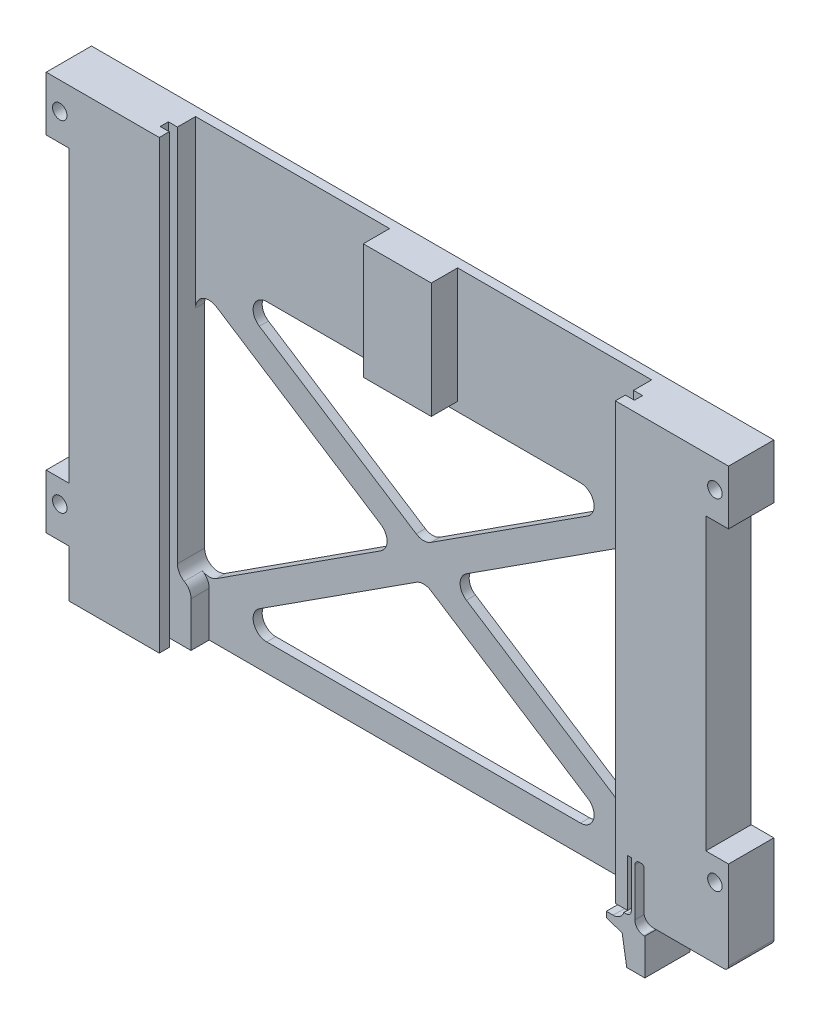
SolidWorks part; units mm, degrees
note: The reader was unsure of these and kept them because the rebuilt part matched: shared geometry of "Sketch4<4>", "Sketch4<3>".
ref_plane "Front Plane" through (0, 0, 0) normal (0, 0, 1) x (1, 0, 0)
ref_plane "Top Plane" through (0, 0, 0) normal (0, 1, 0) x (1, 0, 0)
ref_plane "Right Plane" through (0, 0, 0) normal (1, 0, 0) x (0, 0, -1)
sketch "Sketch2" plane through (0, 0, 0) normal (0, 0, 1) x (1, 0, 0)
  line L4 (140.5, 0) -> (0, 0)
  line L6 (0, 0) -> (0, 98.5)
  line L7 (0, 98.5) -> (140.5, 98.5)
  line L8 (140.5, 98.5) -> (140.5, 0)
  point P2 (0, 0)
  point P5 (20.0537, 0)
  point P6 (0, 0)
  point P7 (154.1532, 0)
  point P8 (0, 0)
  dimension "D1" = 98.5
  dimension "D2" = 140.5
extrude "Boss-Extrude6" add sketch "Sketch2" along normal blind 10
sketch "Sketch1" plane through (0, 0, 0) normal (0, 0, 1) x (1, 0, 0)
  line L1 (20.45, 0) -> (120.05, 0)
  line L2 (17.95, 2.5) -> (17.95, 70.5)
  line L3 (20.45, 73) -> (120.05, 73)
  line L4 (122.55, 2.5) -> (122.55, 70.5)
  line L5 (0, 0) -> (140.5, 0) construction
  line L7 (140.5, 98.5) -> (0, 98.5) construction
  arc A0 (20.45, 0) -> (17.95, 2.5) centre (20.45, 2.5) cw
  arc A1 (17.95, 70.5) -> (20.45, 73) centre (20.45, 70.5) cw
  arc A2 (120.05, 73) -> (122.55, 70.5) centre (120.05, 70.5) cw
  arc A3 (120.05, 0) -> (122.55, 2.5) centre (120.05, 2.5) ccw
  point P7 (17.95, 0)
  point P13 (122.55, 73)
  point P16 (122.55, 0)
  point P21 (70.25, 73)
  point P24 (70.25, 98.5)
  dimension "D3" = 2.5
  dimension "D1" = 104.6
  dimension "D2" = 73
sketch "Sketch10" plane through (0, 0, 0) normal (0, 0, -1) x (-1, 0, 0)
  line L1 (-120.55, 0) -> (-19.95, 0)
  line L2 (-120.55, 0) -> (-120.55, 71)
  line L3 (-120.55, 71) -> (-19.95, 71)
  line L4 (-19.95, 0) -> (-19.95, 71)
  line L6 (0, 0) -> (-140.5, 0) construction
  line L10 (-122.55, 2.5) -> (-122.55, 70.5) construction
  line L11 (-20.45, 73) -> (-120.05, 73) construction
  line L12 (-17.95, 2.5) -> (-17.95, 70.5) construction
  point P4 (-134.9452, 0)
  dimension "D1" = 2
  dimension "D2" = 2
  dimension "D3" = 2
extrude "Cut-Extrude4" cut sketch "Sketch10" against normal through all
sketch "Sketch6" plane through (0, 0, 0) normal (0, 0, 1) x (1, 0, 0)
  line L9 (70.25, 17.5) -> (70.25, 98.5) construction
  line L10 (-2, 92.5) -> (142.5, 92.5) construction
  line L11 (-2, 92.5) -> (-2, 17.5) construction
  line L12 (-2, 17.5) -> (142.5, 17.5) construction
  line L13 (142.5, 92.5) -> (142.5, 17.5) construction
  line L14 (140.5, 98.5) -> (0, 98.5) construction
  circle A4 centre (-2, 92.5) radius 1.6
  circle A5 centre (142.5, 92.5) radius 1.6
  circle A6 centre (142.5, 17.5) radius 1.6
  circle A7 centre (-2, 17.5) radius 1.6
  dimension "D1" = 144.5
  dimension "D4" = 3.2
  dimension "D2" = 75
  dimension "D3" = 17.5
sketch "Sketch3" plane through (0, 0, 0) normal (0, -1, 0) x (1, 0, 0)
  line L0 (70.25, 6) -> (70.25, 0) construction
  line L6 (54.175, 0) -> (-54.175, 0) construction
  line L7 (20.45, 0) -> (120.05, 0) construction
  line L10 (17.95, 7.8) -> (122.55, 7.8)
  line L11 (17.95, 7.8) -> (17.95, 6)
  line L12 (17.95, 6) -> (122.55, 6)
  line L13 (122.55, 7.8) -> (122.55, 6)
  point P5 (70.25, 10)
  point P7 (68.3695, 20.9753)
  point P8 (65.7278, 31.6392)
  point P11 (70.25, 0)
  dimension "D1" = 1.8
  dimension "D2" = 6
extrude "Cut-Extrude1" cut sketch "Sketch3" against normal through all contours L10 L13 L12 L11
sketch "Sketch5" plane through (0, 0, 0) normal (0, 0, 1) x (1, 0, 0)
  line L1 (19.95, 0) -> (120.55, 0)
  line L2 (19.95, 0) -> (19.95, 6)
  line L3 (19.95, 6) -> (120.55, 6)
  line L4 (120.55, 0) -> (120.55, 6)
  line L5 (19.95, 71) -> (120.55, 6) construction
  line L6 (19.95, 6) -> (120.55, 71) construction
  line L8 (19.95, 71) -> (120.55, 6) construction
  line L10 (21.5781, 3.4802) -> (122.1781, 68.4802)
  line L11 (18.3219, 68.4802) -> (118.9219, 3.4802)
  line L12 (18.3219, 8.5198) -> (118.9219, 73.5198)
  line L13 (21.5781, 73.5198) -> (122.1781, 8.5198)
  line L14 (21.5781, 3.4802) -> (18.3219, 8.5198)
  line L15 (122.1781, 68.4802) -> (118.9219, 73.5198)
  line L16 (18.3219, 68.4802) -> (21.5781, 73.5198)
  line L17 (118.9219, 3.4802) -> (122.1781, 8.5198)
  line L18 (19.95, 6) -> (120.55, 71) construction
  point P5 (-5.1527, -2.6914)
  point P6 (-4.0813, -1.4619)
  point P7 (-135.5, 0)
  point P9 (-6.9624, 1.4706)
  point P10 (0, 0)
  point P13 (-5.2214, 0.0156)
  point P15 (-140.5, 0)
  point P16 (-140.2012, 6)
  point P29 (-5, 0)
  point P30 (-5.2473, 6)
  point P32 (-5.5, 6)
  point P35 (-135.5, 6)
  point P36 (0, 0)
  point P38 (-5, 93.5)
  point P40 (-135.5, 93.5)
  dimension "D1" = 6
  dimension "D2" = 3
  dimension "D3" = 3
extrude "Boss-Extrude3" add sketch "Sketch5" along normal blind 2 contours L10 L15 L12 L14 | L11 L17 L13 L16 | L3 L4 L1 L2
sketch "Sketch4" plane through (0, 0, 0) normal (0, 0, 1) x (1, 0, 0)
  line L0 (122.4185, 1.7) -> (123.05, 1.7)
  line L1 (126.85, -0.5) -> (127.05, -0.5)
  line L2 (124.05, 2.7) -> (124.05, 13)
  line L3 (123.25, 13) -> (124.05, 13)
  line L4 (124.85, 12) -> (124.85, 1.5)
  line L6 (123.05, -8.5) -> (122.05, -2.4098)
  line L7 (122.05, -2.4098) -> (118.55, -1.2)
  line L8 (118.55, -1.2) -> (118.55, 0)
  line L9 (122.55, 2.5) -> (122.55, 70.5) construction
  line L10 (127.05, -0.5) -> (127.05, -8.5)
  line L11 (127.05, -8.5) -> (123.05, -8.5)
  line L13 (125.85, 13) -> (126.35, 13)
  line L14 (126.85, 12.5) -> (126.85, 4)
  line L15 (128.85, 2) -> (144.5, 2)
  line L16 (145.5, 3) -> (145.5, 22.5)
  line L17 (145.5, 22.5) -> (140.5, 22.5)
  line L19 (117.55, 2.5) -> (123.25, 2.5)
  line L20 (123.25, 2.5) -> (123.25, 13)
  line L21 (123.25, 2.7) -> (123.25, 13) construction
  line L22 (122.4185, 2.5) -> (123.05, 2.5) construction
  line L23 (117.55, 2.5) -> (117.55, 0)
  line L24 (127.05, -0.5) -> (145.5, -0.5)
  line L26 (140.5, 22.5) -> (124.05, 22.5)
  line L27 (124.05, 22.5) -> (124.05, 13)
  line L28 (145.5, -0.5) -> (145.5, 3)
  line L29 (20.45, 0) -> (120.05, 0) construction
  line L30 (118.55, 0) -> (120.05, 0)
  line L31 (117.55, 0) -> (118.55, 0)
  line L34 (140.5, 98.5) -> (145.5, 98.5)
  line L35 (140.5, 98.5) -> (140.5, 86.5)
  line L36 (140.5, 86.5) -> (145.5, 86.5)
  line L37 (145.5, 98.5) -> (145.5, 86.5)
  line L38 (70.25, 98.5) -> (70.25, 27.8281) construction
  line L39 (-5, 98.5) -> (-5, 86.5)
  line L40 (0, 86.5) -> (-5, 86.5)
  line L41 (0, 98.5) -> (0, 86.5)
  line L42 (0, 98.5) -> (-5, 98.5)
  line L44 (-5, 22.5) -> (0, 22.5)
  line L45 (-5, 22.5) -> (-5, 10.5)
  line L46 (-5, 10.5) -> (0, 10.5)
  line L47 (0, 22.5) -> (0, 10.5)
  line L49 (140.5, 0) -> (140.5, 98.5) construction
  line L50 (120.55, 0) -> (140.5, 0) construction
  arc A0 (120.05, 0) -> (122.55, 2.5) centre (120.05, 2.5) ccw construction
  arc A1 (120.05, 0) -> (122.4185, 1.7) centre (120.05, 2.5) ccw
  arc A2 (126.85, -0.5) -> (124.85, 1.5) centre (126.85, 1.5) cw
  arc A3 (123.05, 1.7) -> (124.05, 2.7) centre (123.05, 2.7) ccw
  arc A4 (126.85, 4) -> (128.85, 2) centre (128.85, 4) ccw
  arc A5 (124.85, 12) -> (125.85, 13) centre (125.85, 12) cw
  arc A6 (126.85, 12.5) -> (126.35, 13) centre (126.35, 12.5) ccw
  arc A7 (144.5, 2) -> (145.5, 3) centre (144.5, 3) ccw
  circle A9 centre (142.5, 17.5) radius 2.75 construction
  circle A12 centre (-2, 92.5) radius 1.6 construction
  circle A13 centre (142.5, 92.5) radius 1.6
  circle A14 centre (-2, 17.5) radius 1.6
  circle A15 centre (-2, 92.5) radius 1.6
  circle A17 centre (142.5, 17.5) radius 1.6
  circle A18 centre (-2, 17.5) radius 1.6 construction
  circle A19 centre (142.5, 92.5) radius 1.6 construction
  circle A20 centre (142.5, 17.5) radius 1.6 construction
  point P2 (139.8, 11.2021)
  point P6 (70.25, 98.5)
  point P27 (0, 0)
  point P29 (142.2439, 17.5)
  point P42 (140.8, 22.5)
  point P44 (0, 0)
  point P46 (-6.5717, 22.5)
  point P50 (0, 0)
  point P63 (0, 0)
  point P75 (140.5, 98.5)
  point P76 (0, 0)
  point P90 (70.25, 27.8281)
  point P93 (140.5, 22.5)
  point P94 (140.5, 22.5)
  point P99 (137.3685, -2.8658)
  point P100 (137.3685, -3.3953)
  point P101 (137, -3.1428)
  point P102 (0, 0)
  point P104 (-2, 92.5)
  point P105 (122.05, -2.4098)
  dimension "D7" = 2
  dimension "D8" = 1
  dimension "D13" = 2
  dimension "D14" = 1
  dimension "D15" = 0.5
  dimension "D20" = 1
  dimension "D25" = 5.5
  dimension "D3" = 1.5
  dimension "D4" = 4
  dimension "D6" = 8
  dimension "D9" = 1.2
  dimension "D11" = 5
  dimension "D12" = 2
  dimension "D17" = 0.8
  dimension "D19" = 11
  dimension "D18" = 2.5
  dimension "D26" = 1
  dimension "D23" = 12
  dimension "D24" = 5
  dimension "D22" = 4
  dimension "D10" = 8.5
  dimension "D21" = 13
  dimension "D5" = 5
  dimension "D27" = 8.5
  dimension "D16" = 0.8
extrude "Cut-Extrude2" cut sketch "Sketch4" along normal through all
extrude "Boss-Extrude7" add sketch "Sketch4<4>" along normal through all contours L15 A7 L16 L17 L26 L27 L2 A3 L0 A1 L30 L8 L7 L6 L11 L10 L1 A2 L4 A5 L13 A6 L14 A4 A17 | L37 L34 L35 L36 A13 | L41 L42 L39 L40 A15 | L47 L44 L45 L46 A14
sketch "Sketch4<4>" plane through (0, 0, 0) normal (0, 0, 1) x (1, 0, 0) same geometry as "Sketch4"
fillet "Fillet1" radius 3 12 edges at (70.25, 42.0717, 1) (64.7221, 38.5, 1) (70.25, 34.9283, 1) (75.7779, 38.5, 1) (19.95, 9.5717, 1) (25.4779, 6, 1) (115.0221, 6, 1) (120.55, 9.5717, 1) (120.55, 67.4283, 1) (115.0221, 71, 1) (25.4779, 71, 1) (19.95, 67.4283, 1)
extrude "Boss-Extrude2" add sketch "Sketch4<3>" along normal through all
sketch "Sketch4<3>" plane through (0, 0, 0) normal (0, 0, 1) x (1, 0, 0) same geometry as "Sketch4"
sketch "Sketch7" plane through (0, 0, 10) normal (0, 0, 1) x (1, 0, 0)
  line L1 (19.95, 71) -> (120.55, 71)
  line L2 (19.95, 71) -> (19.95, 98.5)
  line L3 (19.95, 98.5) -> (120.55, 98.5)
  line L4 (120.55, 71) -> (120.55, 98.5)
  line L5 (145.5, 98.5) -> (-5, 98.5) construction
  point P5 (133.6838, 98.5)
  point P7 (5, 93.5)
  point P11 (135.5, 93.5)
extrude "Cut-Extrude3" cut sketch "Sketch7" against normal up to surface (8 mm away) up to face at (70.25, 17.0092, 2)
sketch "Sketch8" plane through (0, 0, 2) normal (0, 0, 1) x (1, 0, 0)
  line L0 (120.55, 98.5) -> (19.95, 98.5) construction
  line L5 (70.25, 17.5) -> (70.25, 98.5) construction
  line L8 (62.75, 98.5) -> (77.75, 98.5)
  line L9 (62.75, 98.5) -> (62.75, 73)
  line L10 (62.75, 73) -> (77.75, 73)
  line L11 (77.75, 98.5) -> (77.75, 73)
  line L12 (20.45, 73) -> (120.05, 73) construction
  line L14 (70.25, 98.5) -> (70.25, 12.3809) construction
  point P4 (27.9813, 98.5)
  point P10 (70.25, 73)
  point P15 (70.25, 98.5)
  dimension "D1" = 15
extrude "Boss-Extrude4" add sketch "Sketch8" along normal up to surface (5.8 mm away) up to face at (121.55, 50.5, 7.8)
sketch "Sketch9" plane through (0, 0, 2) normal (0, 0, 1) x (1, 0, 0)
  line L0 (117.55, 12.0818) -> (117.55, 2.5)
  line L1 (117.55, 2.5) -> (120.55, 2.5)
  line L3 (120.55, 2.5) -> (120.55, 15.0818)
  line L4 (19.95, 0) -> (22.95, 0)
  line L5 (19.95, 0) -> (117.55, 0) construction
  line L6 (22.95, 0) -> (22.95, 12.0818)
  line L9 (19.95, 15.0818) -> (19.95, 0)
  arc A1 (117.55, 12.0818) -> (120.55, 15.0818) centre (117.55, 15.0818) ccw
  arc A3 (19.95, 15.0818) -> (22.95, 12.0818) centre (22.95, 15.0818) ccw
  arc A4 (19.95, 15.0818) -> (24.5781, 12.5621) centre (22.95, 15.0818) ccw construction
  arc A6 (115.9219, 12.5621) -> (120.55, 15.0818) centre (117.55, 15.0818) ccw construction
  dimension "D1" = 3
  dimension "D2" = 3
extrude "Boss-Extrude5" add sketch "Sketch9" along normal up to surface (4 mm away) up to face at (18.95, 49.25, 6)
fillet "Fillet2" radius 3 2 edges at (117.55, 12.0818, 4) (22.95, 12.0818, 4)
equation "\"D16@Sketch4\"=\"D17@Sketch4\""
equation "\"D2@Sketch9\"=\"D1@Sketch9\""
equation "\"D2@Sketch10\"=\"D1@Sketch10\""
equation "\"D3@Sketch10\"=\"D1@Sketch10\""
